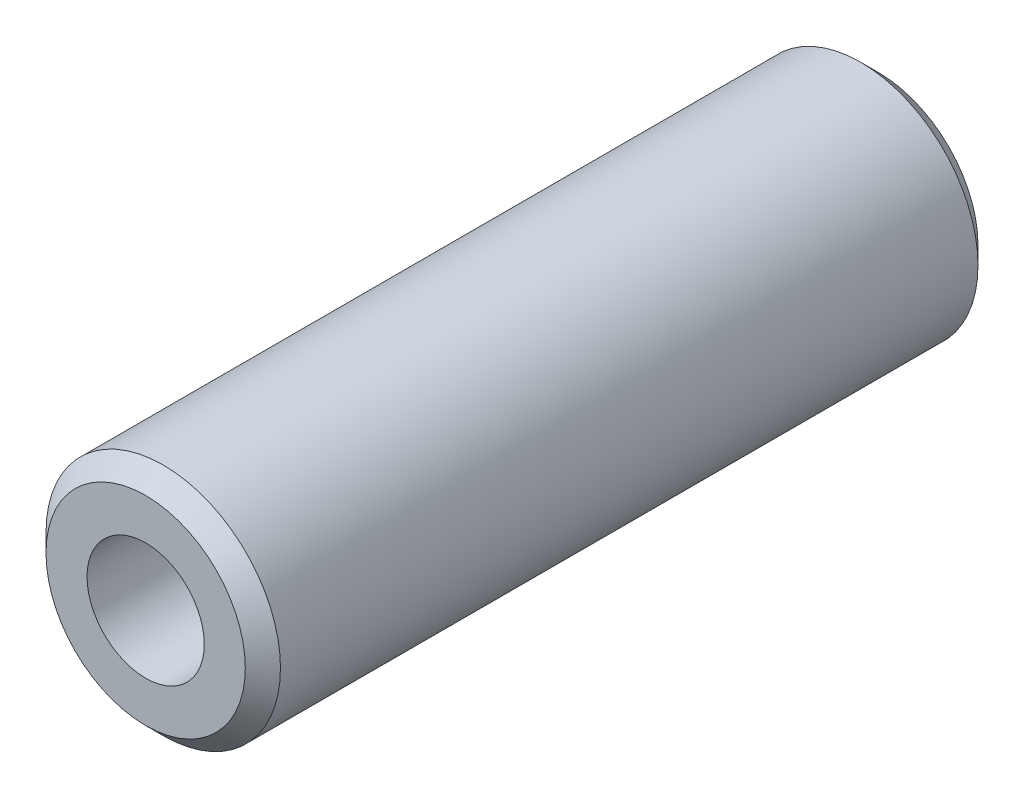
SolidWorks part; units mm, degrees
ref_plane "Front Plane" through (0, 0, 0) normal (0, 0, 1) x (1, 0, 0)
ref_plane "Top Plane" through (0, 0, 0) normal (0, 1, 0) x (1, 0, 0)
ref_plane "Right Plane" through (0, 0, 0) normal (1, 0, 0) x (0, 0, -1)
sketch "Sketch1" plane through (0, 0, 0) normal (0, 0, 1) x (1, 0, 0)
  line L0 (-4, 0) -> (4, 0) construction
  line L5 (0, 4) -> (0, -4) construction
  circle A1 centre (0, 0) radius 4
  point P7 (-4, 0)
  point P8 (4, 0)
  point P12 (0, -4)
  point P13 (0, 4)
  dimension "Diameter" = 8
sketch "Sketch2" plane through (0, 0, 0) normal (1, 0, 0) x (0, 0, -1)
  line L10 (-12.5, 0) -> (12.5, 0) construction
  line L11 (12.5, -4) -> (-12.5, -4)
  line L12 (12.5, -4) -> (12.5, 4)
  line L13 (12.5, 4) -> (-12.5, 4)
  line L14 (-12.5, -4) -> (-12.5, 4)
  line L15 (-2.5, 4) -> (-2.5, -4)
  line L16 (2.5, 4) -> (2.5, -4)
  line L17 (-2.5, 0) -> (2.5, 0) construction
  line L18 (-11.9, 4) -> (-12.5, 3.4) construction
  point P0 (0, 0)
  point P4 (0, 0)
  point P28 (0, 0)
  dimension "Chamfer Typ," = 45
  dimension "Length" = 25
  dimension "Chamfer Length" = 0.6
  dimension "D1" = 10
sketch "Sketch3" plane through (0, 0, 0) normal (0, 0, 1) x (1, 0, 0)
  circle A0 centre (0, 0) radius 4 construction
  circle A1 centre (0, 0) radius 4
extrude "Boss-Extrude1" add sketch "Sketch3" along normal up to vertex (-12.5 mm away) and the other way up to vertex (12.5 mm away) up to point (0, 4, -12.5) other way up to point (0, 4, -12.5)
chamfer "Chamfer1" distance 0.6 angle 45 2 edges at (4, 0, -12.5) (4, 0, 12.5)
ref_axis "Axis1" through (0, 0, 11.9) along (0, 0, -1)
sketch "Sketch4" plane through (0, 0, -12.5) normal (0, 0, -1) x (-1, 0, 0)
  circle A0 centre (0, 0) radius 2
  dimension "D1" = 4
extrude "Cut-Extrude1" cut sketch "Sketch4" against normal blind 42
equation "\"D1@Chamfer1\"=\"Chamfer Length@Sketch2\""
equation "\"D2@Chamfer1\"=\"Chamfer Typ,@Sketch2\""
equation "\"Chamfer Length@Sketch2\" = \"Diameter@Sketch1\" * .075"
